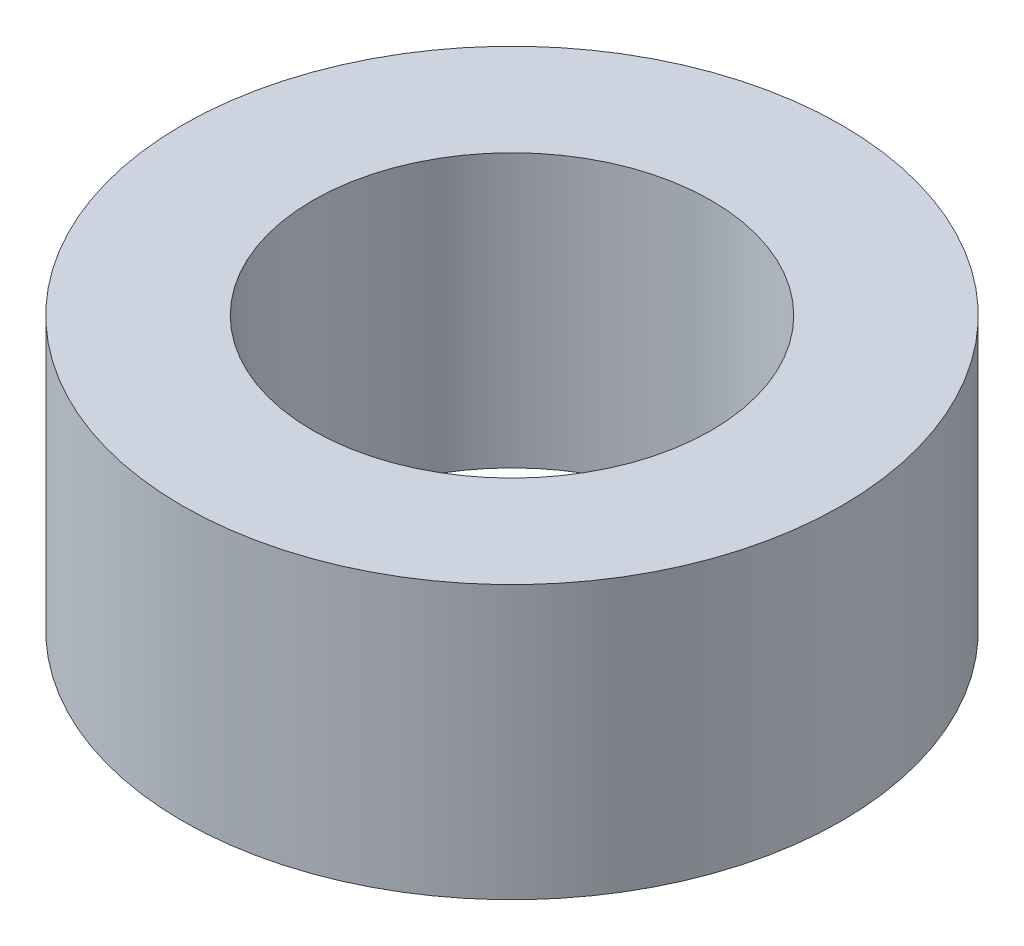
SolidWorks part; units mm, degrees
ref_plane "Front Plane" through (0, 0, 0) normal (0, 0, 1) x (1, 0, 0)
ref_plane "Top Plane" through (0, 0, 0) normal (0, 1, 0) x (1, 0, 0)
ref_plane "Right Plane" through (0, 0, 0) normal (1, 0, 0) x (0, 0, -1)
sketch "Sketch1" plane through (0, 0, 0) normal (0, 1, 0) x (1, 0, 0)
  circle A0 centre (0, 0) radius 22.5
  dimension "SLEEVE_OD" = 45
extrude "Boss-Extrude1" add sketch "Sketch1" along normal blind 18.6244
sketch "Sketch2" plane through (0, 0, 0) normal (0, 1, 0) x (1, 0, 0)
  circle A0 centre (0, 0) radius 13.5973
  dimension "BORE_D" = 27.1945
extrude "Cut-Extrude1" cut sketch "Sketch2" along normal through all
chamfer "Chamfer1" distance 3.0824 angle 67.721 rebuild error yes
